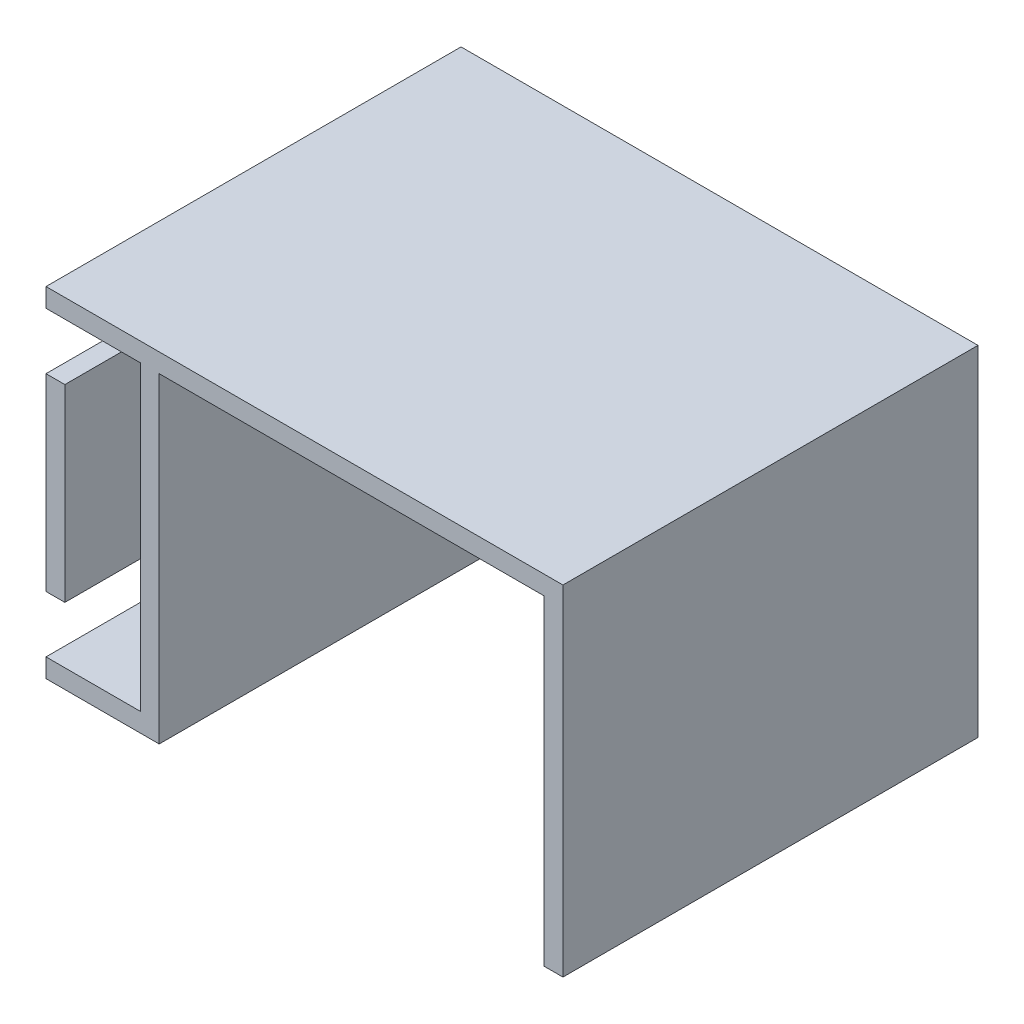
SolidWorks part; units mm, degrees
ref_plane "Front Plane" through (0, 0, 0) normal (0, 0, 1) x (1, 0, 0)
ref_plane "Top Plane" through (0, 0, 0) normal (0, 1, 0) x (1, 0, 0)
ref_plane "Right Plane" through (0, 0, 0) normal (1, 0, 0) x (0, 0, -1)
sketch "Sketch1" plane through (0, 0, 0) normal (0, 0, 1) x (1, 0, 0)
  line L1 (-10.1, -10.1) -> (10.1, -10.1)
  line L2 (-10.1, -10.1) -> (-10.1, 10.1)
  line L3 (-10.1, 10.1) -> (10.1, 10.1)
  line L4 (10.1, -10.1) -> (10.1, 10.1)
  line L5 (-10.1, -10.1) -> (10.1, 10.1) construction
  line L6 (-10.1, 10.1) -> (10.1, -10.1) construction
  point P0 (0, 0)
  dimension "D1" = 20.2
  dimension "D2" = 20.2
sketch "Sketch2" plane through (0, 0, 0) normal (0, 0, 1) x (1, 0, 0)
  line L0 (0, 0) -> (10.1, 0) construction
  line L1 (0, 0) -> (0, 10.1) construction
  line L2 (10.1, 0) -> (10.1, -10) construction
  line L4 (11.2, -6.9) -> (11.2, 11.1)
  line L5 (11.2, 11.1) -> (-11.2, 11.1)
  line L7 (-11.2, 11.1) -> (-11.2, -5.9)
  line L8 (-11.2, -5.9) -> (-15.2, -5.9)
  line L9 (-15.2, -5.9) -> (-15.2, 10.1)
  line L10 (-15.2, 10.1) -> (-16.2, 10.1)
  line L11 (-16.2, 10.1) -> (-16.2, -6.9)
  line L13 (-10.2, -6.9) -> (-16.2, -6.9)
  line L14 (-10.2, -6.9) -> (-10.2, 10.1)
  line L15 (-10.2, 10.1) -> (10.2, 10.1)
  line L16 (10.2, 10.1) -> (10.2, -6.9)
  line L19 (-10, -8.9) -> (11.2, -8.9) construction
  line L21 (10.2, -6.9) -> (11.2, -6.9)
  dimension "D2" = 20
  dimension "D3" = 18
  dimension "D4" = 22.4
  dimension "D5" = 6
  dimension "D6" = 17
  dimension "D7" = 4
  dimension "D8" = 1
  dimension "D9" = 1
  dimension "D10" = 1
  dimension "D11" = 17
  dimension "D12" = 1
  dimension "D14" = 10.1
  dimension "D15" = 10.1
extrude "Boss-Extrude2" add sketch "Sketch2" along normal blind 22 separate body
sketch "Sketch3" plane through (0, 0, 0) normal (0, 0, -1) x (-1, 0, 0)
  line L1 (15.2, 10.1) -> (11.2, 10.1)
  line L2 (15.2, 10.1) -> (15.2, -5.9)
  line L3 (15.2, -5.9) -> (11.2, -5.9)
  line L4 (11.2, 10.1) -> (11.2, -5.9)
extrude "Boss-Extrude3" add sketch "Sketch3" against normal blind 1
sketch "Sketch6" plane through (0, 0, 22) normal (0, 0, 1) x (1, 0, 0)
  line L1 (-11.2, 11.1) -> (-16.2, 11.1)
  line L2 (-11.2, 11.1) -> (-11.2, 10.1)
  line L3 (-11.2, 10.1) -> (-16.2, 10.1)
  line L4 (-16.2, 11.1) -> (-16.2, 10.1)
extrude "Boss-Extrude4" add sketch "Sketch6" against normal up to surface (22 mm away) up to face at (-3.24, 3.5, 0)
sketch "Sketch7" plane through (-16.2, 0, 0) normal (-1, 0, 0) x (0, 0, 1)
  line L0 (22, -6.9) -> (22, -5.9) construction
  line L1 (22, 11.1) -> (22, -6.9) construction
  line L3 (0, 10.1) -> (0, -10.1) construction
  line L4 (0, -5.9) -> (1, -5.9) construction
  line L5 (22, 11.1) -> (22, 10.1) construction
  line L6 (1, -5.9) -> (22, -5.9)
  line L7 (1, -5.9) -> (1, -2.9)
  line L8 (1, -2.9) -> (22, -2.9)
  line L9 (22, -5.9) -> (22, -2.9)
  line L10 (1, -2.9) -> (1, 7.6506) construction
  line L12 (22, 10.1) -> (1, 10.1)
  line L13 (22, 10.1) -> (22, 7.1)
  line L14 (22, 7.1) -> (1, 7.1)
  line L15 (1, 10.1) -> (1, 7.1)
  dimension "D1" = 1
  dimension "D2" = 1
  dimension "D3" = 1
  dimension "D4" = 3
  dimension "D5" = 3
extrude "Cut-Extrude1" cut sketch "Sketch7" against normal up to next
